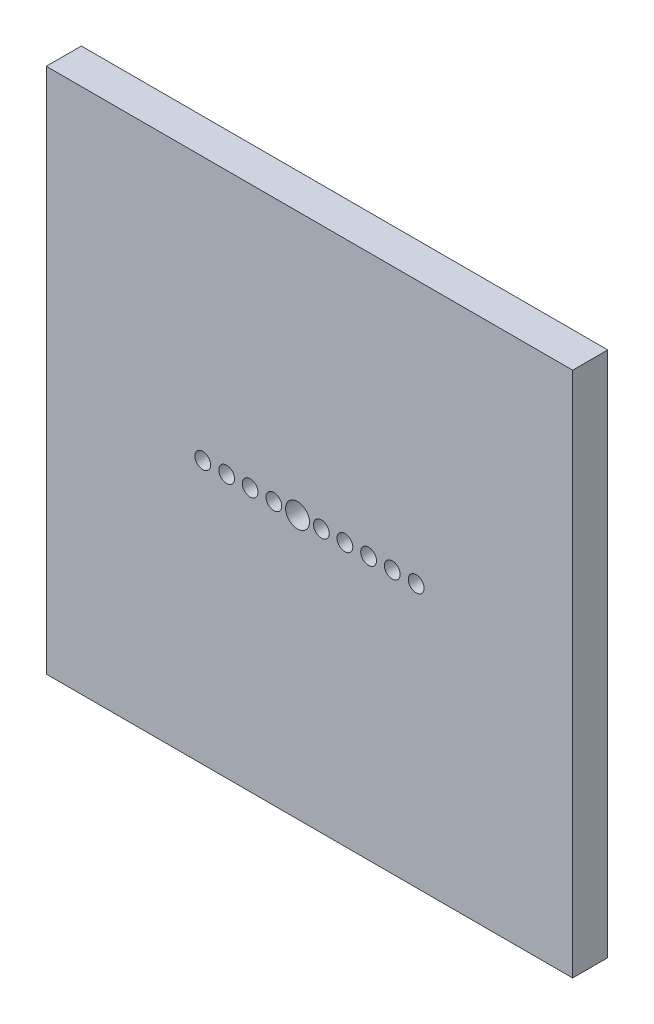
SolidWorks part; units mm, degrees
ref_plane "Plan de face" through (0, 0, 0) normal (0, 0, 1) x (1, 0, 0)
ref_plane "Plan de dessus" through (0, 0, 0) normal (0, 1, 0) x (1, 0, 0)
ref_plane "Plan de droite" through (0, 0, 0) normal (1, 0, 0) x (0, 0, -1)
sketch "Esquisse2" plane through (0, 0, 0) normal (0, 0, 1) x (1, 0, 0)
  line L1 (-15, -15) -> (15, -15)
  line L2 (-15, -15) -> (-15, 15)
  line L3 (-15, 15) -> (15, 15)
  line L4 (15, -15) -> (15, 15)
  line L5 (-15, -15) -> (15, 15) construction
  line L6 (-15, 15) -> (15, -15) construction
  point P0 (0, 0)
extrude "Boss.-Extru.1" add sketch "Esquisse2" along normal blind 2
sketch "Esquisse3" plane through (0, 0, 2) normal (0, 0, 1) x (1, 0, 0)
  circle A0 centre (-6.08, 0) radius 0.45
  circle A1 centre (-4.72, 0) radius 0.45
  circle A2 centre (-3.38, 0) radius 0.45
  circle A3 centre (-2.03, 0) radius 0.45
  circle A4 centre (-0.68, 0) radius 0.68
  circle A5 centre (0.68, 0) radius 0.45
  circle A6 centre (2.02, 0) radius 0.45
  circle A7 centre (3.37, 0) radius 0.45
  circle A8 centre (4.72, 0) radius 0.45
  circle A9 centre (6.08, 0) radius 0.45
extrude "Enlèv. mat.-Extru.1" cut sketch "Esquisse3" against normal blind 10
